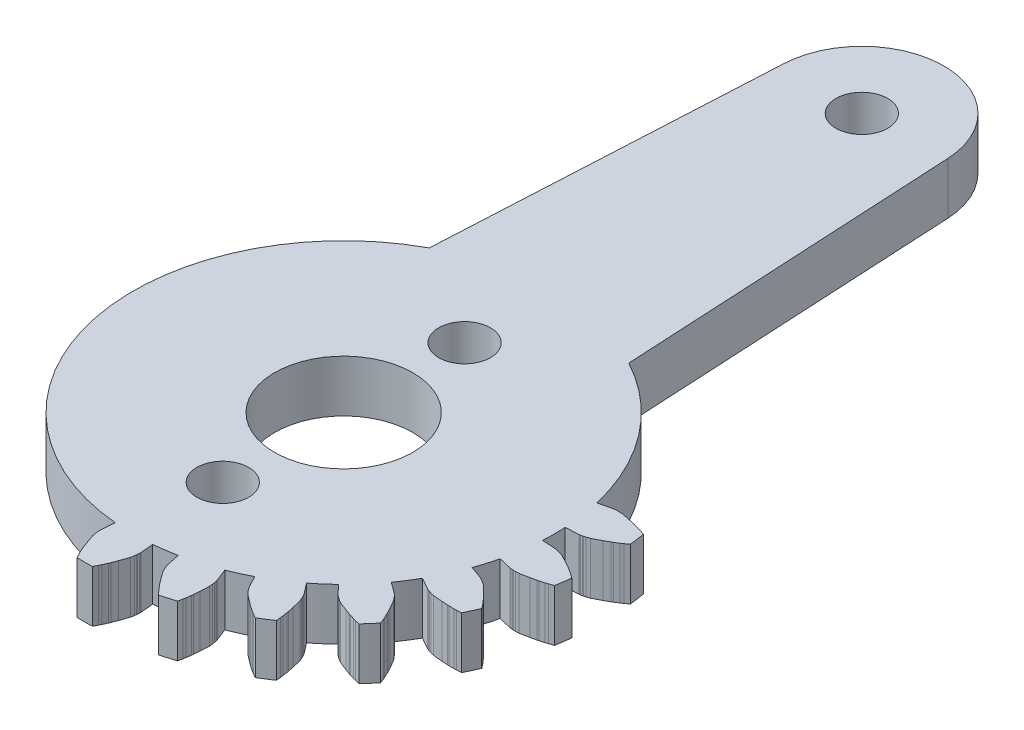
SolidWorks part; units mm, degrees
material "普通碳钢"
ref_plane "前视" through (0, 0, 0) normal (0, 0, 1) x (1, 0, 0)
ref_plane "上视" through (0, 0, 0) normal (0, 1, 0) x (1, 0, 0)
ref_plane "右视" through (0, 0, 0) normal (1, 0, 0) x (0, 0, -1)
sketch "草图1" plane through (0, 0, 0) normal (0, 1, 0) x (1, 0, 0)
  line L0 (39.751, 40.5224) -> (39.6866, 41.2679)
  line L1 (39.6866, 41.2679) -> (39.6851, 41.3287)
  line L2 (39.6851, 41.3287) -> (39.6859, 41.3577)
  line L3 (39.6859, 41.3577) -> (39.6916, 41.4528)
  line L4 (39.6916, 41.4528) -> (39.6929, 41.4698)
  line L5 (39.6929, 41.4698) -> (39.6966, 41.5042)
  line L6 (39.6966, 41.5042) -> (39.712, 41.6258)
  line L7 (39.712, 41.6258) -> (39.7121, 41.6267)
  line L8 (39.7121, 41.6267) -> (39.7482, 41.8247)
  line L9 (39.9295, 42.3366) -> (40.044, 42.6442)
  line L10 (40.044, 42.6442) -> (40.0454, 42.6478)
  line L11 (40.0454, 42.6478) -> (40.0855, 42.7398)
  line L12 (40.0855, 42.7398) -> (40.1995, 42.9971)
  line L13 (41.9203, 40.5224) -> (41.9848, 41.2679)
  line L14 (41.9848, 41.2679) -> (41.9862, 41.3287)
  line L15 (41.9862, 41.3287) -> (41.9855, 41.3577)
  line L16 (41.9855, 41.3577) -> (41.9797, 41.4528)
  line L17 (41.9797, 41.4528) -> (41.9784, 41.4698)
  line L18 (41.9784, 41.4698) -> (41.9748, 41.5042)
  line L19 (41.9748, 41.5042) -> (41.9594, 41.6258)
  line L20 (41.9594, 41.6258) -> (41.9592, 41.6267)
  line L21 (41.9592, 41.6267) -> (41.9231, 41.8247)
  line L22 (41.7419, 42.3366) -> (41.6274, 42.6442)
  line L23 (41.6274, 42.6442) -> (41.626, 42.6478)
  line L24 (41.626, 42.6478) -> (41.5858, 42.7398)
  line L25 (41.5858, 42.7398) -> (41.4718, 42.9971)
  circle A0 centre (40.8357, 28.3833) radius 12.1875 construction
  arc A1 (39.751, 40.5224) -> (41.9203, 40.5224) centre (40.8357, 28.3833) cw
  arc A2 (41.9231, 41.8247) -> (41.7419, 42.3366) centre (25.8953, 36.4382) ccw
  arc A4 (39.9295, 42.3366) -> (39.7482, 41.8247) centre (55.7761, 36.4382) ccw
  arc A5 (40.2653, 43.1347) -> (40.1995, 42.9971) centre (42.6892, 41.8899) ccw
  arc A6 (40.3945, 43.3768) -> (40.2653, 43.1347) centre (48.1168, 39.1026) ccw
  arc A11 (41.4718, 42.9971) -> (41.406, 43.1347) centre (38.9822, 41.8899) ccw
  arc A12 (41.406, 43.1347) -> (41.2769, 43.3768) centre (33.5546, 39.1026) ccw
  arc A13 (41.2769, 43.3768) -> (40.3945, 43.3768) centre (40.8357, 28.3833) ccw
  dimension "D1" = 24.375
extrude "凸台-拉伸1" add sketch "草图1" along normal blind 3 contours A4 L8 L7 L6 L5 L4 L3 L2 L1 L0 A1 L13 L14 L15 L16 L17 L18 L19 L20 L21 A2 L22 L23 L24 L25 A11 A12 A13 A6 A5 L12 L11 L10 L9
sketch "草图2" plane through (0, 0, 0) normal (0, -1, 0) x (1, 0, 0)
  circle A0 centre (40.8357, -28.3833) radius 12.1875
  circle A1 centre (40.8357, -28.3833) radius 4
  circle A2 centre (40.8357, -28.3833) radius 7 construction
  circle A3 centre (40.8357, -21.3833) radius 1.5
  circle A4 centre (40.8357, -35.3833) radius 1.5
  dimension "D1" = 8
  dimension "D2" = 24.375
  dimension "D3" = 14
  dimension "D4" = 3
  dimension "D5" = 3
extrude "凸台-拉伸2" add sketch "草图2" against normal blind 3
pattern_circular "阵列(圆周)2" count 22 over 360 about axis through (40.8357, 0, -28.3833) along (0, 1, 0) of "凸台-拉伸1"
sketch "草图3" plane through (0, 0, 0) normal (0, -1, 0) x (-1, 0, 0)
  circle A0 centre (-40.8357, 28.3833) radius 13.75
  dimension "D1" = 27.5
sketch "草图5" plane through (0, 0, 0) normal (0, -1, 0) x (1, 0, 0)
  line L0 (40.8357, -19.8833) -> (40.8357, -63.1398) construction
  line L1 (45.5857, -58.6327) -> (46.6107, -39.1157)
  line L2 (36.0857, -58.6327) -> (35.0607, -39.1157)
  circle A0 centre (40.8357, -21.3833) radius 1.5 construction
  circle A2 centre (40.8357, -28.3833) radius 12.1875 construction
  arc A3 (53.0056, -29.0373) -> (53.0056, -27.7293) centre (40.8357, -28.3833) ccw construction
  arc A4 (36.0857, -58.6327) -> (45.5857, -58.6327) centre (40.8357, -58.3833) ccw
  circle A5 centre (40.8357, -58.3833) radius 1.5
  arc A6 (35.0607, -39.1157) -> (46.6107, -39.1157) centre (40.8357, -28.3833) ccw
  dimension "D4" = 3
  dimension "D1" = 11.55
  dimension "D2" = 9.5
  dimension "D3" = 30
extrude "凸台-拉伸3" add sketch "草图5" against normal blind 3
sketch "草图7" plane through (0, 0, 0) normal (0, -1, 0) x (1, 0, 0)
  line L0 (36.0857, -58.6327) -> (34.9723, -37.4337) construction
  line L1 (35.0751, -39.3907) -> (36.0857, -58.6327) construction
  line L2 (45.5857, -58.6327) -> (46.7591, -36.2892) construction
  line L3 (45.5857, -58.6327) -> (46.5962, -39.3907) construction
  line L4 (35.0607, -39.1157) -> (35.0751, -39.3907)
  line L5 (35.0751, -39.3907) -> (34.8365, -39.8437)
  line L6 (34.8365, -39.8437) -> (33.6211, -45.0698)
  line L7 (33.6211, -45.0698) -> (23.2947, -35.4215)
  line L8 (23.2947, -35.4215) -> (25.1891, -22.1682)
  line L9 (25.1891, -22.1682) -> (31.4308, -11.204)
  line L10 (31.4308, -11.204) -> (37.9696, -9.817)
  line L11 (37.9696, -9.817) -> (39.751, -16.2441)
  line L12 (46.6107, -39.1157) -> (46.5962, -39.3907)
  line L13 (46.5962, -39.3907) -> (47.0142, -42.3632)
  line L14 (52.3284, -32.4394) -> (55.4375, -32.4394)
  line L15 (55.4375, -32.4394) -> (53.5277, -41.7128)
  line L16 (53.5277, -41.7128) -> (47.0142, -42.3632)
  arc A0 (35.0607, -39.1157) -> (39.751, -16.2441) centre (40.8357, -28.3833) cw
  circle A1 centre (40.8357, -28.3833) radius 4 construction
  circle A2 centre (40.8357, -28.3833) radius 12.1875 construction
  arc A3 (46.6107, -39.1157) -> (52.3284, -32.4394) centre (40.8357, -28.3833) ccw
extrude "切除-拉伸1" cut sketch "草图7" against normal blind 3
sketch "草图8" plane through (0, 0, 0) normal (0, -1, 0) x (1, 0, 0)
  line L0 (40.8357, -35.3833) -> (40.8357, -21.3833)
